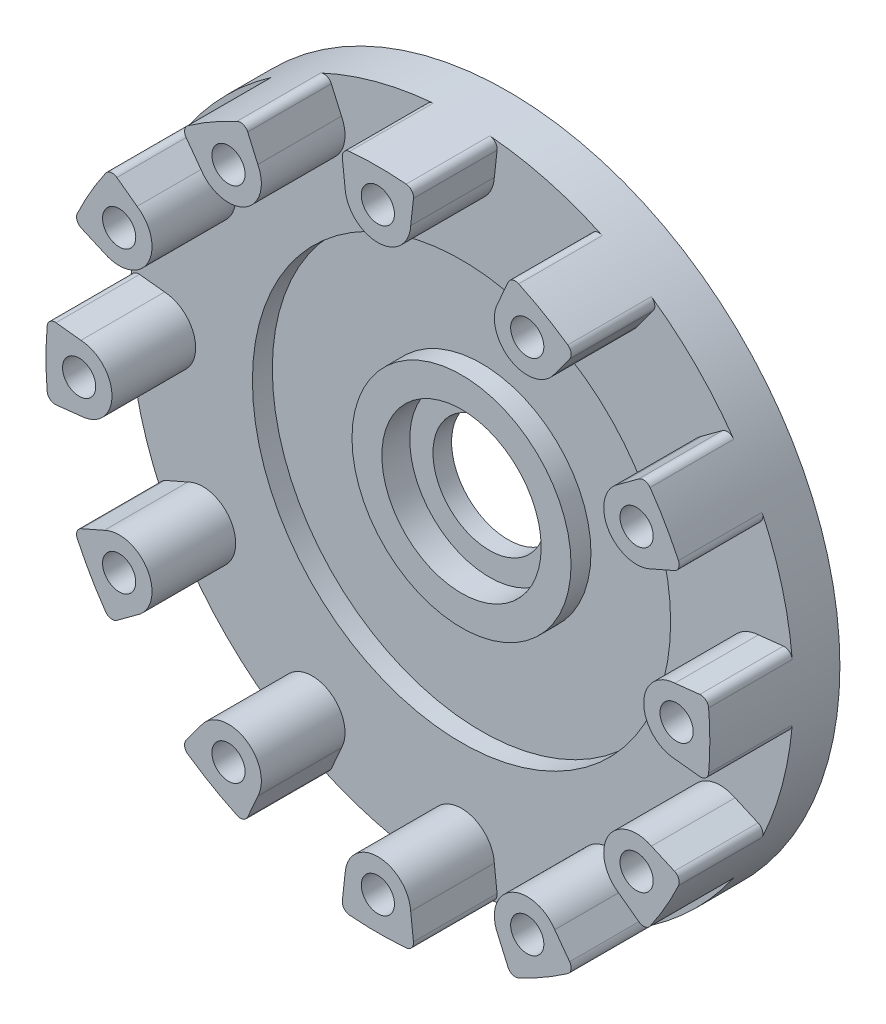
SolidWorks part; units mm, degrees
ref_plane "Front Plane" through (0, 0, 0) normal (0, 0, 1) x (1, 0, 0)
ref_plane "Top Plane" through (0, 0, 0) normal (0, 1, 0) x (1, 0, 0)
ref_plane "Right Plane" through (0, 0, 0) normal (1, 0, 0) x (0, 0, -1)
sketch "Sketch1" plane through (0, 0, 0) normal (0, 0, 1) x (1, 0, 0)
  circle A0 centre (0, 0) radius 50
  dimension "D1" = 100
extrude "Boss-Extrude1" add sketch "Sketch1" against normal blind 7
sketch "Sketch2" plane through (0, 0, 0) normal (0, 0, 1) x (1, 0, 0)
  line L0 (0, 0) -> (44.7277, 4.9425) construction
  line L1 (44.7277, 4.9425) -> (48.4901, 5.3583)
  line L2 (0, 0) -> (44.7277, -4.9425) construction
  line L3 (44.7277, -4.9425) -> (48.4901, -5.3583)
  circle A0 centre (0, 0) radius 45 construction
  arc A1 (44.7277, 4.9425) -> (44.7277, -4.9425) centre (45, 0) ccw
  arc A2 (44.7277, -4.9425) -> (44.7277, 4.9425) centre (0, 0) ccw construction
  circle A3 centre (0, 0) radius 50 construction
  arc A4 (49.8175, 4.2679) -> (49.8175, -4.2679) centre (0, 0) cw
  arc A5 (48.4901, -5.3583) -> (49.8175, -4.2679) centre (48.6219, -4.1655) ccw
  arc A6 (48.4901, 5.3583) -> (49.8175, 4.2679) centre (48.6219, 4.1655) cw
  circle A7 centre (45, 0) radius 2.5
  point P13 (49.6975, -5.4917)
  point P16 (49.6975, 5.4917)
  dimension "D1" = 90
  dimension "D2" = 4.95
  dimension "D3" = 1.2
  dimension "D4" = 5
extrude "Boss-Extrude2" add sketch "Sketch2" along normal blind 12.6
pattern_circular "CirPattern1" count 12 over 360 about axis through (0, 0, -7) along (0, 0, 1) of "Boss-Extrude2" reverse direction yes
sketch "Sketch3" plane through (0, 0, 0) normal (0, 0, 1) x (1, 0, 0)
  circle A0 centre (0, 0) radius 12
  dimension "D1" = 24
extrude "Cut-Extrude1" cut sketch "Sketch3" against normal through all
sketch "Sketch4" plane through (0, 0, 0) normal (0, 0, 1) x (1, 0, 0)
  line L0 (-16.5, 0) -> (-31.5, 0) construction
  circle A0 centre (0, 0) radius 24 construction
  circle A1 centre (0, 0) radius 31.5
  circle A2 centre (0, 0) radius 16.5
  point P7 (-24, 0)
  point P8 (-24, 0)
  dimension "D1" = 48
  dimension "D2" = 15
extrude "Cut-Extrude2" cut sketch "Sketch4" against normal blind 3
sketch "Sketch5" plane through (0, 0, 0) normal (0, 0, 1) x (1, 0, 0)
  circle A0 centre (0, 0) radius 12
  circle A1 centre (0, 0) radius 8.5
  circle A2 centre (0, 0) radius 12 construction
  dimension "D1" = 17
extrude "Boss-Extrude3" add sketch "Sketch5" against normal up to surface (2.8 mm away) from offset 4.2 up to face at (12, 0, -7) offset against normal yes
